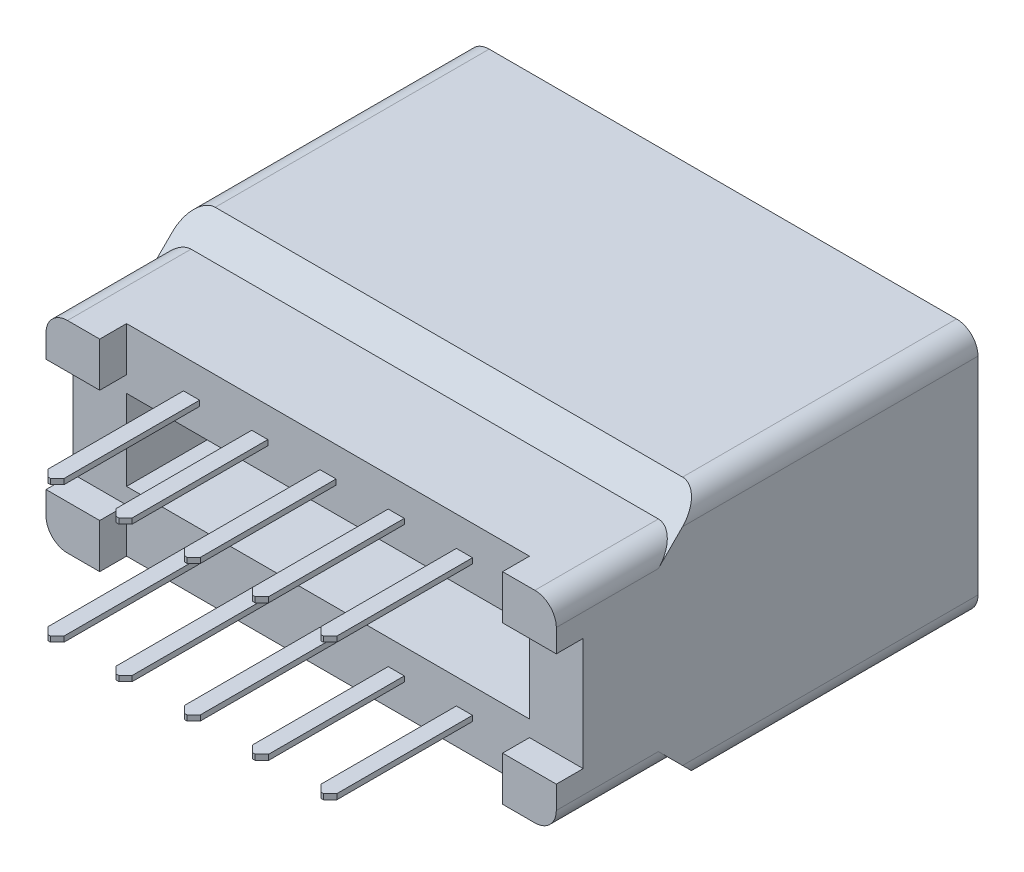
SolidWorks part; units mm, degrees
ref_plane "Спереди" through (0, 0, 0) normal (0, 0, 1) x (1, 0, 0)
ref_plane "Сверху" through (0, 0, 0) normal (0, 1, 0) x (1, 0, 0)
ref_plane "Справа" through (0, 0, 0) normal (1, 0, 0) x (0, 0, -1)
sketch "Эскиз1" plane through (0, 0, 0) normal (0, 0, 1) x (1, 0, 0)
  line L1 (9.5, -4.65) -> (-9.5, -4.65)
  line L2 (9.5, -4.65) -> (9.5, 4.65)
  line L3 (9.5, 4.65) -> (-9.5, 4.65)
  line L4 (-9.5, -4.65) -> (-9.5, 4.65)
  line L5 (9.5, -4.65) -> (-9.5, 4.65) construction
  line L6 (9.5, 4.65) -> (-9.5, -4.65) construction
  point P0 (0, 0)
  dimension "D1" = 19
  dimension "D2" = 9.3
extrude "Бобышка-Вытянуть1" add sketch "Эскиз1" along normal blind 10.2
sketch "Эскиз2" plane through (0, 0, 10.2) normal (0, 0, 1) x (1, 0, 0)
  line L0 (-9.5, 4.65) -> (-9.5, -4.65) construction
  line L5 (9.5, -3.75) -> (-9.5, -3.75)
  line L6 (9.5, -3.75) -> (9.5, 3.75)
  line L7 (9.5, 3.75) -> (-9.5, 3.75)
  line L8 (-9.5, -3.75) -> (-9.5, 3.75)
  line L9 (9.5, -3.75) -> (-9.5, 3.75) construction
  line L10 (9.5, 3.75) -> (-9.5, -3.75) construction
  point P0 (0, 0)
  dimension "D1" = 7.5
extrude "Бобышка-Вытянуть2" add sketch "Эскиз2" along normal blind 5.5
sketch "Эскиз3" plane through (0, 0, 15.7) normal (0, 0, 1) x (1, 0, 0)
  line L0 (-9.5, 3.75) -> (-9.5, -3.75) construction
  line L1 (9.5, -2.1) -> (-9.5, -2.1)
  line L2 (9.5, -2.1) -> (9.5, 2.1)
  line L3 (9.5, 2.1) -> (-9.5, 2.1)
  line L4 (-9.5, -2.1) -> (-9.5, 2.1)
  line L5 (9.5, -2.1) -> (-9.5, 2.1) construction
  line L6 (9.5, 2.1) -> (-9.5, -2.1) construction
  point P0 (0, 0)
  dimension "D1" = 4.2
extrude "Вырез-Вытянуть1" cut sketch "Эскиз3" against normal blind 1
sketch "Эскиз4" plane through (0, 0, 15.7) normal (0, 0, 1) x (1, 0, 0)
  line L0 (9.5, 3.75) -> (-9.5, 3.75) construction
  line L1 (7.5, -3.75) -> (-7.5, -3.75)
  line L2 (7.5, -3.75) -> (7.5, 3.75)
  line L3 (7.5, 3.75) -> (-7.5, 3.75)
  line L4 (-7.5, -3.75) -> (-7.5, 3.75)
  line L5 (7.5, -3.75) -> (-7.5, 3.75) construction
  line L6 (7.5, 3.75) -> (-7.5, -3.75) construction
  point P0 (0, 0)
  dimension "D1" = 15
extrude "Вырез-Вытянуть2" cut sketch "Эскиз4" against normal blind 1
chamfer "Фаска1" distance 0.9 angle 45 2 edges at (0, -3.75, 10.2) (0, 3.75, 10.2)
sketch "Эскиз5" plane through (0, 0, 14.7) normal (0, 0, 1) x (1, 0, 0)
  line L1 (7.5, -1.5) -> (-7.5, -1.5)
  line L2 (7.5, -1.5) -> (7.5, 1.5)
  line L3 (7.5, 1.5) -> (-7.5, 1.5)
  line L4 (-7.5, -1.5) -> (-7.5, 1.5)
  line L5 (7.5, -1.5) -> (-7.5, 1.5) construction
  line L6 (7.5, 1.5) -> (-7.5, -1.5) construction
  point P0 (0, 0)
  dimension "D1" = 15
  dimension "D2" = 3
extrude "Вырез-Вытянуть3" cut sketch "Эскиз5" against normal blind 3.5
sketch "Эскиз6" plane through (0, 0, 14.7) normal (0, 0, 1) x (1, 0, 0)
  line L0 (2.84, 2.64) -> (2.24, 2.64)
  line L1 (0.3, 2.64) -> (-0.3, 2.64)
  line L2 (0.3, 2.64) -> (0.3, 2.44)
  line L3 (0.3, 2.44) -> (-0.3, 2.44)
  line L4 (-0.3, 2.64) -> (-0.3, 2.44)
  line L5 (0.3, 2.64) -> (-0.3, 2.44) construction
  line L6 (0.3, 2.44) -> (-0.3, 2.64) construction
  line L7 (2.84, 2.64) -> (2.84, 2.44)
  line L8 (2.84, 2.44) -> (2.24, 2.44)
  line L9 (2.24, 2.64) -> (2.24, 2.44)
  line L10 (2.84, 2.64) -> (2.24, 2.44) construction
  line L11 (2.84, 2.44) -> (2.24, 2.64) construction
  line L12 (5.38, 2.64) -> (4.78, 2.64)
  line L13 (5.38, 2.64) -> (5.38, 2.44)
  line L14 (5.38, 2.44) -> (4.78, 2.44)
  line L15 (4.78, 2.64) -> (4.78, 2.44)
  line L16 (5.38, 2.64) -> (4.78, 2.44) construction
  line L17 (5.38, 2.44) -> (4.78, 2.64) construction
  line L18 (2.84, -2.44) -> (2.24, -2.44)
  line L19 (2.84, -2.44) -> (2.84, -2.64)
  line L20 (2.84, -2.64) -> (2.24, -2.64)
  line L21 (2.24, -2.44) -> (2.24, -2.64)
  line L22 (2.84, -2.44) -> (2.24, -2.64) construction
  line L23 (2.84, -2.64) -> (2.24, -2.44) construction
  line L24 (5.38, -2.44) -> (4.78, -2.44)
  line L25 (5.38, -2.44) -> (5.38, -2.64)
  line L26 (5.38, -2.64) -> (4.78, -2.64)
  line L27 (4.78, -2.44) -> (4.78, -2.64)
  line L28 (5.38, -2.44) -> (4.78, -2.64) construction
  line L29 (5.38, -2.64) -> (4.78, -2.44) construction
  line L30 (0.3, -2.44) -> (-0.3, -2.44)
  line L31 (0.3, -2.44) -> (0.3, -2.64)
  line L32 (0.3, -2.64) -> (-0.3, -2.64)
  line L33 (-0.3, -2.44) -> (-0.3, -2.64)
  line L34 (0.3, -2.44) -> (-0.3, -2.64) construction
  line L35 (0.3, -2.64) -> (-0.3, -2.44) construction
  line L36 (-2.24, 2.64) -> (-2.84, 2.64)
  line L37 (-2.24, 2.64) -> (-2.24, 2.44)
  line L38 (-2.24, 2.44) -> (-2.84, 2.44)
  line L39 (-2.84, 2.64) -> (-2.84, 2.44)
  line L40 (-2.24, 2.64) -> (-2.84, 2.44) construction
  line L41 (-2.24, 2.44) -> (-2.84, 2.64) construction
  line L42 (-4.78, 2.64) -> (-5.38, 2.64)
  line L43 (-4.78, 2.64) -> (-4.78, 2.44)
  line L44 (-4.78, 2.44) -> (-5.38, 2.44)
  line L45 (-5.38, 2.64) -> (-5.38, 2.44)
  line L46 (-4.78, 2.64) -> (-5.38, 2.44) construction
  line L47 (-4.78, 2.44) -> (-5.38, 2.64) construction
  line L48 (-2.24, -2.44) -> (-2.84, -2.44)
  line L49 (-2.24, -2.44) -> (-2.24, -2.64)
  line L50 (-2.24, -2.64) -> (-2.84, -2.64)
  line L51 (-2.84, -2.44) -> (-2.84, -2.64)
  line L52 (-2.24, -2.44) -> (-2.84, -2.64) construction
  line L53 (-2.24, -2.64) -> (-2.84, -2.44) construction
  line L54 (-4.78, -2.44) -> (-5.38, -2.44)
  line L55 (-4.78, -2.44) -> (-4.78, -2.64)
  line L56 (-4.78, -2.64) -> (-5.38, -2.64)
  line L57 (-5.38, -2.44) -> (-5.38, -2.64)
  line L58 (-4.78, -2.44) -> (-5.38, -2.64) construction
  line L59 (-4.78, -2.64) -> (-5.38, -2.44) construction
  line L60 (0.3, -2.44) -> (-0.3, -2.44)
  line L61 (0.3, -2.44) -> (0.3, -2.64)
  line L62 (0.3, -2.64) -> (-0.3, -2.64)
  line L63 (-0.3, -2.44) -> (-0.3, -2.64)
  line L64 (0.3, -2.44) -> (-0.3, -2.64) construction
  line L65 (0.3, -2.64) -> (-0.3, -2.44) construction
  point P0 (0, 2.54)
  point P9 (2.54, 2.54)
  point P14 (5.08, 2.54)
  point P19 (2.54, -2.54)
  point P24 (5.08, -2.54)
  point P29 (0, -2.54)
  point P34 (-2.54, 2.54)
  point P39 (-5.08, 2.54)
  point P44 (-2.54, -2.54)
  point P49 (-5.08, -2.54)
  point P54 (0, -2.54)
  dimension "D1" = 0.6
  dimension "D2" = 0.2
  dimension "D3" = 2.54
  dimension "D4" = 3
  dimension "D5" = 2
  dimension "D6" = 3
  dimension "D7" = 2
extrude "Бобышка-Вытянуть3" add sketch "Эскиз6" along normal blind 5.3 contours L42 L45 L44 L43 | L36 L39 L38 L37 | L1 L4 L3 L2 | L0 L9 L8 L7 | L12 L15 L14 L13 | L54 L57 L56 L55 | L48 L51 L50 L49 | L30 L33 L32 L31 | L18 L21 L20 L19 | L24 L27 L26 L25 region at (2.54, 2.54, 14.7) region at (0, 2.54, 14.7) region at (5.08, 2.54, 14.7) region at (2.54, -2.54, 14.7) region at (5.08, -2.54, 14.7) region at (0, -2.54, 14.7) region at (-2.54, 2.54, 14.7) region at (-5.08, 2.54, 14.7) region at (-2.54, -2.54, 14.7) region at (-5.08, -2.54, 14.7)
chamfer "Фаска2" distance 0.25 angle 45 20 edges at (5.38, -2.54, 20) (4.78, -2.54, 20) (2.84, -2.54, 20) (2.24, -2.54, 20) (0.3, -2.54, 20) (-0.3, -2.54, 20) (-2.24, -2.54, 20) (-2.84, -2.54, 20) (-4.78, -2.54, 20) (-5.38, -2.54, 20) (5.38, 2.54, 20) (4.78, 2.54, 20) (2.84, 2.54, 20) (2.24, 2.54, 20) (0.3, 2.54, 20) (-0.3, 2.54, 20) (-2.84, 2.54, 20) (-2.24, 2.54, 20) (-4.78, 2.54, 20) (-5.38, 2.54, 20)
sketch "Эскиз7" plane through (0, 0, 0) normal (0, 0, -1) x (-1, 0, 0)
  line L1 (7.8, -0.95) -> (-7.8, -0.95)
  line L2 (7.8, -0.95) -> (7.8, 0.95)
  line L3 (7.8, 0.95) -> (-7.8, 0.95)
  line L4 (-7.8, -0.95) -> (-7.8, 0.95)
  line L5 (7.8, -0.95) -> (-7.8, 0.95) construction
  line L6 (7.8, 0.95) -> (-7.8, -0.95) construction
  point P0 (0, 0)
  dimension "D1" = 15.6
  dimension "D2" = 1.9
extrude "Вырез-Вытянуть4" cut sketch "Эскиз7" against normal blind 8.8
chamfer "Фаска3" distance 1.4 angle 38 4 edges at (0, -0.95, 0) (-7.8, 0, 0) (0, 0.95, 0) (7.8, 0, 0) first distance on face at (0, -0.95, 4.4) first distance on face at (-7.8, 0, 4.4) first distance on face at (0, 0.95, 4.4) first distance on face at (7.8, 0, 4.4)
sketch "Эскиз8" plane through (0, 0, 0) normal (0, 0, -1) x (-1, 0, 0)
  line L0 (3.34, -3.65) -> (1.74, -3.65)
  line L1 (0.8, -3.65) -> (-0.8, -3.65)
  line L2 (0.8, -3.65) -> (0.8, 3.65)
  line L3 (0.8, 3.65) -> (-0.8, 3.65)
  line L4 (-0.8, -3.65) -> (-0.8, 3.65)
  line L5 (0.8, -3.65) -> (-0.8, 3.65) construction
  line L6 (0.8, 3.65) -> (-0.8, -3.65) construction
  line L7 (3.34, -3.65) -> (3.34, 3.65)
  line L8 (3.34, 3.65) -> (1.74, 3.65)
  line L9 (1.74, -3.65) -> (1.74, 3.65)
  line L10 (3.34, -3.65) -> (1.74, 3.65) construction
  line L11 (3.34, 3.65) -> (1.74, -3.65) construction
  line L12 (5.88, -3.65) -> (4.28, -3.65)
  line L13 (5.88, -3.65) -> (5.88, 3.65)
  line L14 (5.88, 3.65) -> (4.28, 3.65)
  line L15 (4.28, -3.65) -> (4.28, 3.65)
  line L16 (5.88, -3.65) -> (4.28, 3.65) construction
  line L17 (5.88, 3.65) -> (4.28, -3.65) construction
  line L18 (-1.74, -3.65) -> (-3.34, -3.65)
  line L19 (-1.74, -3.65) -> (-1.74, 3.65)
  line L20 (-1.74, 3.65) -> (-3.34, 3.65)
  line L21 (-3.34, -3.65) -> (-3.34, 3.65)
  line L22 (-1.74, -3.65) -> (-3.34, 3.65) construction
  line L23 (-1.74, 3.65) -> (-3.34, -3.65) construction
  line L24 (-4.28, -3.65) -> (-5.88, -3.65)
  line L25 (-4.28, -3.65) -> (-4.28, 3.65)
  line L26 (-4.28, 3.65) -> (-5.88, 3.65)
  line L27 (-5.88, -3.65) -> (-5.88, 3.65)
  line L28 (-4.28, -3.65) -> (-5.88, 3.65) construction
  line L29 (-4.28, 3.65) -> (-5.88, -3.65) construction
  point P0 (0, 0)
  point P7 (2.54, 0)
  point P12 (5.08, 0)
  point P17 (-2.54, 0)
  point P22 (-5.08, 0)
  dimension "D1" = 1.6
  dimension "D2" = 7.3
  dimension "D3" = 3
  dimension "D4" = 3
extrude "Вырез-Вытянуть5" cut sketch "Эскиз8" against normal blind 8.8
sketch "Эскиз9" plane through (0, 0, 0) normal (0, 0, -1) x (-1, 0, 0)
  line L5 (-5.88, 3.65) -> (-4.28, 2.4438) construction
  line L6 (-4.28, 2.0438) -> (-4.28, 3.65) construction
  line L7 (-4.28, 3.65) -> (-5.88, 2.4438) construction
  line L8 (-5.88, 3.65) -> (-5.88, 2.0438) construction
  line L9 (-8.8938, 2.0438) -> (-5.88, 2.0438) construction
  line L10 (-3.93, 2.2438) -> (-6.23, 2.2438)
  line L11 (-3.93, 2.2438) -> (-3.93, 3.85)
  line L12 (-3.93, 3.85) -> (-6.23, 3.85)
  line L13 (-6.23, 2.2438) -> (-6.23, 3.85)
  line L14 (-3.93, 2.2438) -> (-6.23, 3.85) construction
  line L15 (-3.93, 3.85) -> (-6.23, 2.2438) construction
  line L16 (-1.39, 2.2438) -> (-3.69, 2.2438)
  line L17 (-1.39, 2.2438) -> (-1.39, 3.85)
  line L18 (-1.39, 3.85) -> (-3.69, 3.85)
  line L19 (-3.69, 2.2438) -> (-3.69, 3.85)
  line L20 (-3.34, 3.65) -> (-1.74, 2.4438) construction
  line L21 (-1.74, 3.65) -> (-3.34, 2.4438) construction
  line L22 (-1.39, 2.2438) -> (-3.69, 3.85) construction
  line L23 (-1.39, 3.85) -> (-3.69, 2.2438) construction
  line L24 (1.15, 2.2438) -> (-1.15, 2.2438)
  line L25 (1.15, 2.2438) -> (1.15, 3.85)
  line L26 (1.15, 3.85) -> (-1.15, 3.85)
  line L27 (-1.15, 2.2438) -> (-1.15, 3.85)
  line L28 (-0.8, 3.65) -> (0.8, 2.4438) construction
  line L29 (0.8, 3.65) -> (-0.8, 2.4438) construction
  line L30 (1.15, 2.2438) -> (-1.15, 3.85) construction
  line L31 (1.15, 3.85) -> (-1.15, 2.2438) construction
  line L32 (3.69, 2.2438) -> (1.39, 2.2438)
  line L33 (3.69, 2.2438) -> (3.69, 3.85)
  line L34 (3.69, 3.85) -> (1.39, 3.85)
  line L35 (1.39, 2.2438) -> (1.39, 3.85)
  line L36 (1.74, 3.65) -> (3.34, 2.4438) construction
  line L37 (3.34, 3.65) -> (1.74, 2.4438) construction
  line L38 (3.69, 2.2438) -> (1.39, 3.85) construction
  line L39 (3.69, 3.85) -> (1.39, 2.2438) construction
  line L40 (6.23, 2.2438) -> (3.93, 2.2438)
  line L41 (6.23, 2.2438) -> (6.23, 3.85)
  line L42 (6.23, 3.85) -> (3.93, 3.85)
  line L43 (3.93, 2.2438) -> (3.93, 3.85)
  line L44 (4.28, 3.65) -> (5.88, 2.4438) construction
  line L45 (5.88, 3.65) -> (4.28, 2.4438) construction
  line L46 (6.23, 2.2438) -> (3.93, 3.85) construction
  line L47 (6.23, 3.85) -> (3.93, 2.2438) construction
  line L48 (-1.39, -3.8562) -> (-3.69, -3.8562)
  line L49 (-1.39, -3.8562) -> (-1.39, -2.25)
  line L50 (-1.39, -2.25) -> (-3.69, -2.25)
  line L51 (-3.69, -3.8562) -> (-3.69, -2.25)
  line L52 (-3.34, -2.45) -> (-1.74, -3.6562) construction
  line L53 (-1.74, -2.45) -> (-3.34, -3.6562) construction
  line L54 (-1.39, -3.8562) -> (-3.69, -2.25) construction
  line L55 (-1.39, -2.25) -> (-3.69, -3.8562) construction
  line L56 (1.15, -3.8562) -> (-1.15, -3.8562)
  line L57 (1.15, -3.8562) -> (1.15, -2.25)
  line L58 (1.15, -2.25) -> (-1.15, -2.25)
  line L59 (-1.15, -3.8562) -> (-1.15, -2.25)
  line L60 (-0.8, -2.45) -> (0.8, -3.6562) construction
  line L61 (0.8, -2.45) -> (-0.8, -3.6562) construction
  line L62 (1.15, -3.8562) -> (-1.15, -2.25) construction
  line L63 (1.15, -2.25) -> (-1.15, -3.8562) construction
  line L64 (3.69, -3.8562) -> (1.39, -3.8562)
  line L65 (3.69, -3.8562) -> (3.69, -2.25)
  line L66 (3.69, -2.25) -> (1.39, -2.25)
  line L67 (1.39, -3.8562) -> (1.39, -2.25)
  line L68 (1.74, -2.45) -> (3.34, -3.6562) construction
  line L69 (3.34, -2.45) -> (1.74, -3.6562) construction
  line L70 (3.69, -3.8562) -> (1.39, -2.25) construction
  line L71 (3.69, -2.25) -> (1.39, -3.8562) construction
  line L72 (6.23, -3.8562) -> (3.93, -3.8562)
  line L73 (6.23, -3.8562) -> (6.23, -2.25)
  line L74 (6.23, -2.25) -> (3.93, -2.25)
  line L75 (3.93, -3.8562) -> (3.93, -2.25)
  line L76 (4.28, -2.45) -> (5.88, -3.6562) construction
  line L77 (5.88, -2.45) -> (4.28, -3.6562) construction
  line L78 (6.23, -3.8562) -> (3.93, -2.25) construction
  line L79 (6.23, -2.25) -> (3.93, -3.8562) construction
  line L80 (-3.93, -3.8562) -> (-6.23, -3.8562)
  line L81 (-3.93, -3.8562) -> (-3.93, -2.25)
  line L82 (-3.93, -2.25) -> (-6.23, -2.25)
  line L83 (-6.23, -3.8562) -> (-6.23, -2.25)
  line L84 (-5.88, -2.45) -> (-4.28, -3.6562) construction
  line L85 (-4.28, -2.45) -> (-5.88, -3.6562) construction
  line L86 (-3.93, -3.8562) -> (-6.23, -2.25) construction
  line L87 (-3.93, -2.25) -> (-6.23, -3.8562) construction
  point P11 (-5.08, 3.0469)
  point P26 (-2.54, 3.0469)
  point P35 (0, 3.0469)
  point P44 (2.54, 3.0469)
  point P53 (5.08, 3.0469)
  point P62 (-2.54, -3.0531)
  point P71 (0, -3.0531)
  point P80 (2.54, -3.0531)
  point P89 (5.08, -3.0531)
  point P98 (-5.08, -3.0531)
  dimension "D1" = 0.4
  dimension "D2" = 2.3
  dimension "D3" = 0.2
  dimension "D4" = 5
  dimension "D5" = 2
extrude "Вырез-Вытянуть6" cut sketch "Эскиз9" against normal blind 8.8
fillet "Скругление1" radius 0.8 8 edges at (-9.5, -4.65, 5.1) (-9.5, -3.75, 13.4) (-9.5, 4.65, 5.1) (-9.5, 3.75, 13.4) (9.5, -3.75, 13.4) (9.5, -4.65, 5.1) (9.5, 4.65, 5.1) (9.5, 3.75, 13.4)
sketch "Эскиз10" plane through (0, 0, 0) normal (0, 0, -1) x (-1, 0, 0)
  line L0 (-9.5, -3.85) -> (-9.5, 3.85) construction
  line L1 (-9.1, 3.75) -> (-7.3, 3.75)
  line L2 (-9.1, 3.75) -> (-9.1, 2.45)
  line L3 (-9.1, 2.45) -> (-7.3, 2.45)
  line L4 (-7.3, 3.75) -> (-7.3, 2.45)
  line L5 (-8.7, 4.65) -> (8.7, 4.65) construction
  line L6 (8.7, -4.65) -> (-8.7, -4.65) construction
  line L7 (9.1, 3.75) -> (7.3, 3.75)
  line L8 (9.1, 3.75) -> (9.1, 2.45)
  line L9 (9.1, 2.45) -> (7.3, 2.45)
  line L10 (7.3, 3.75) -> (7.3, 2.45)
  line L11 (9.1, -3.75) -> (7.3, -3.75)
  line L12 (9.1, -3.75) -> (9.1, -2.45)
  line L13 (9.1, -2.45) -> (7.3, -2.45)
  line L14 (7.3, -3.75) -> (7.3, -2.45)
  line L15 (-9.1, -3.75) -> (-7.3, -3.75)
  line L16 (-9.1, -3.75) -> (-9.1, -2.45)
  line L17 (-9.1, -2.45) -> (-7.3, -2.45)
  line L18 (-7.3, -3.75) -> (-7.3, -2.45)
  line L19 (9.5, 3.85) -> (9.5, -3.85) construction
  dimension "D1" = 0.4
  dimension "D2" = 0.9
  dimension "D3" = 1.8
  dimension "D4" = 1.3
  dimension "D5" = 0.4
  dimension "D6" = 0.9
  dimension "D7" = 0.4
  dimension "D8" = 0.9
  dimension "D9" = 0.4
  dimension "D10" = 0.9
extrude "Вырез-Вытянуть7" cut sketch "Эскиз10" against normal blind 8.8
